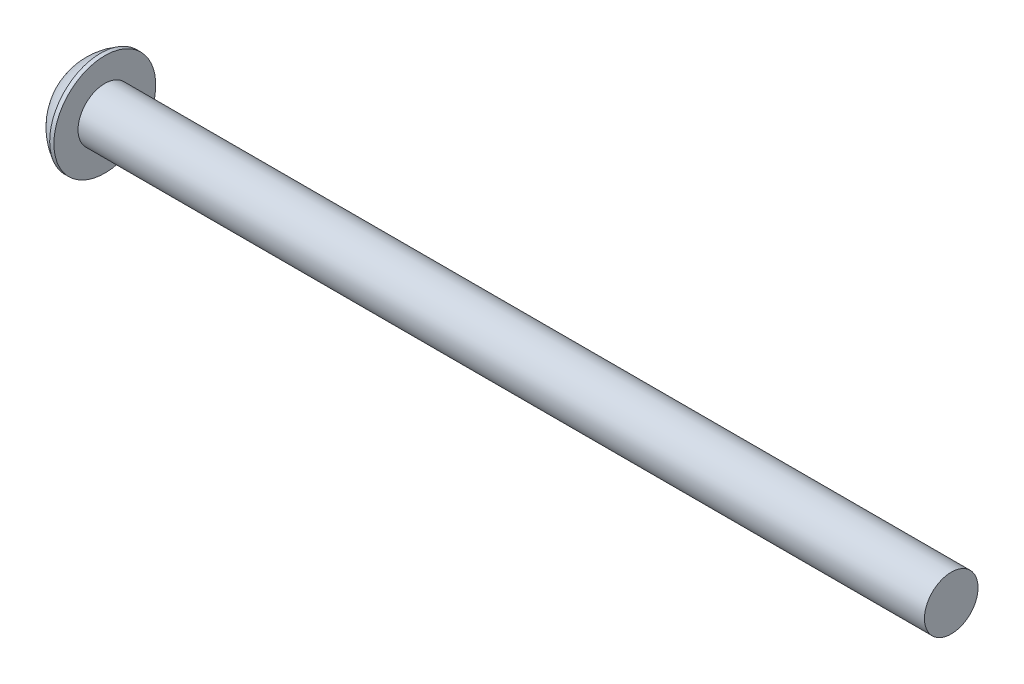
SolidWorks part; units mm, degrees
material "Alloy Steel"
ref_plane "Front" through (0, 0, 0) normal (0, 0, 1) x (1, 0, 0)
ref_plane "Top" through (0, 0, 0) normal (0, 1, 0) x (1, 0, 0)
ref_plane "Right" through (0, 0, 0) normal (1, 0, 0) x (0, 0, -1)
sketch "Sketch1" plane through (0, 0, 0) normal (0, 0, 1) x (1, 0, 0)
  line L0 (0, 0) -> (76.9366, 0)
  line L1 (76.9366, 0) -> (76.9366, 2.413)
  line L2 (76.9366, 2.413) -> (0.7366, 2.413)
  line L3 (0.7366, 2.413) -> (0.7366, 4.5847)
  line L4 (0.7366, 4.5847) -> (0.3556, 4.5847)
  line L5 (-1.8288, 2.413) -> (-1.8288, 1.8288)
  line L6 (0, 0) -> (4.2959, 0) construction
  line L7 (-1.8288, 1.8288) -> (0, 0)
  arc A0 (-1.8288, 2.413) -> (0.3556, 4.5847) centre (2.7515, -0.0097) cw
  dimension "Head Radius" = 5.1816
  dimension "Edge Flat" = 0.381
  dimension "Thread Length" = 76.2
  dimension "Head Diameter" = 9.1694
  dimension "Thread Diameter" = 4.826
  dimension "D6" = 45
  dimension "Head Height" = 2.5654
  dimension "Hex Chamfer Radius" = 1.8288
revolve "Revolve1" add sketch "Sketch1" angle 360 about L6
sketch "Sketch2" plane through (-1.8288, 0, 0) normal (-1, 0, 0) x (0, 0, 1)
  line L1 (1.8331, 0) -> (0.9165, 1.5875)
  line L2 (0.9165, 1.5875) -> (-0.9165, 1.5875)
  line L3 (-0.9165, 1.5875) -> (-1.8331, 0)
  line L4 (-1.8331, 0) -> (-0.9165, -1.5875)
  line L5 (-0.9165, -1.5875) -> (0.9165, -1.5875)
  line L6 (0.9165, -1.5875) -> (1.8331, 0)
  circle A0 centre (0, 0) radius 1.5875 construction
  dimension "Hex Width" = 3.175
extrude "Cut-Extrude1" cut sketch "Sketch2" against normal up to vertex (1.8288 mm away) up to point (0, 0, 0)
other "Freeze***"
